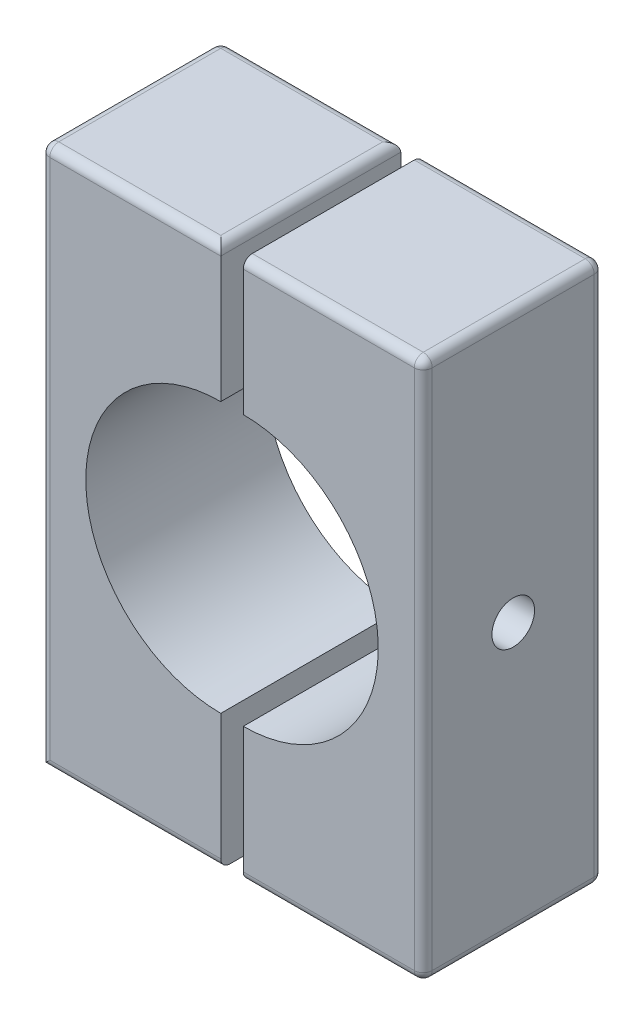
SolidWorks part; units mm, degrees
material "Teak"
ref_plane "Front Plane" through (0, 0, 0) normal (0, 0, 1) x (1, 0, 0)
ref_plane "Top Plane" through (0, 0, 0) normal (0, 1, 0) x (1, 0, 0)
ref_plane "Right Plane" through (0, 0, 0) normal (1, 0, 0) x (0, 0, -1)
sketch "Sketch1" plane through (0, 0, 0) normal (0, 0, 1) x (1, 0, 0)
  line L0 (-9.9618, -64.9931) -> (-9.9618, -94.9931)
  line L1 (-49.9618, 25.0069) -> (-9.9618, 25.0069)
  line L2 (-49.9618, 25.0069) -> (-49.9618, -94.9931)
  line L3 (-49.9618, -94.9931) -> (-9.9618, -94.9931)
  line L4 (-9.9618, 25.0069) -> (-9.9618, -4.9931)
  line L5 (-4.9618, 25.0069) -> (35.0382, 25.0069)
  line L6 (-4.9618, 25.0069) -> (-4.9618, -4.9931)
  line L7 (-4.9618, -94.9931) -> (35.0382, -94.9931)
  line L8 (35.0382, 25.0069) -> (35.0382, -94.9931)
  line L9 (-4.9618, -64.9931) -> (-4.9618, -94.9931)
  arc A0 (-9.9618, -4.9931) -> (-9.9618, -64.9931) centre (-9.9618, -34.9931) ccw
  arc A1 (-4.9618, -4.9931) -> (-4.9618, -64.9931) centre (-4.9618, -34.9931) cw
  point P11 (0, 0)
  dimension "D7" = 30
  dimension "D1" = 40
  dimension "D2" = 40
  dimension "D3" = 120
  dimension "D4" = 120
  dimension "D5" = 60
  dimension "D6" = 60
  dimension "D8" = 5
  dimension "D9" = 60
extrude "Boss-Extrude1" add sketch "Sketch1" along normal blind 40
fillet "Fillet1" radius 2 6 edges at (15.0382, -94.9931, 0) (35.0382, -34.9931, 0) (15.0382, 25.0069, 0) (15.0382, 25.0069, 40) (35.0382, 25.0069, 20) (35.0382, -34.9931, 40)
fillet "Fillet2" radius 2 8 edges at (-9.9618, 25.0069, 20) (-29.9618, 25.0069, 40) (-49.9618, 25.0069, 20) (-29.9618, 25.0069, 0) (-29.9618, -94.9931, 40) (-49.9618, -34.9931, 40) (-49.9618, -34.9931, 0) (-29.9618, -94.9931, 0)
fillet "Fillet3" radius 2 4 edges at (14.0382, -94.9931, 40) (34.4524, -94.9931, 39.4142) (34.4524, -94.4073, 0.5858) (35.0382, -94.9931, 20)
sketch "Sketch2" plane through (-49.9618, 0, 0) normal (-1, 0, 0) x (0, 0, 1)
  line L0 (2, 25.0069) -> (38, 25.0069) construction
  line L1 (38, -94.9931) -> (2, -94.9931) construction
  line L2 (38, -94.9931) -> (38, 23.0069) construction
  circle A0 centre (20, -34.9931) radius 3.5
  point P2 (22.2288, -34.9931)
  point P7 (0, 0)
  point P10 (0, 0)
  dimension "D1" = 60
  dimension "D2" = 60
  dimension "D3" = 18
extrude "Cut-Extrude2" cut sketch "Sketch2" against normal blind 8
sketch "Sketch3" plane through (35.0382, 0, 0) normal (1, 0, 0) x (0, 0, -1)
  line L0 (-38, -92.9931) -> (-2, -92.9931) construction
  line L1 (-2, -92.9931) -> (-2, 23.0069) construction
  line L2 (-38, 23.0069) -> (-38, -92.9931) construction
  circle A0 centre (-20, -34.9931) radius 4.7393
  point P2 (0, 0)
  point P7 (0, 0)
  point P9 (-38, -35.2841)
  dimension "D1" = 58
  dimension "D2" = 36
  dimension "D3" = 18
extrude "Cut-Extrude3" cut sketch "Sketch3" against normal blind 8
